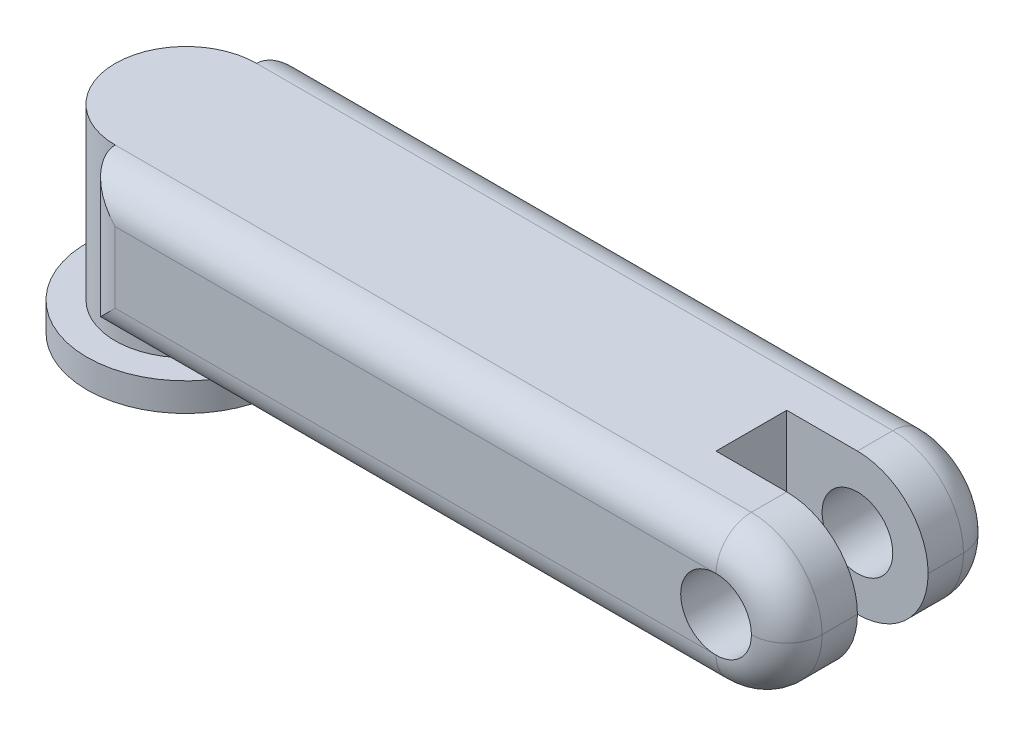
SolidWorks part; units mm, degrees
ref_plane "Front Plane" through (0, 0, 0) normal (0, 0, 1) x (1, 0, 0)
ref_plane "Top Plane" through (0, 0, 0) normal (0, 1, 0) x (1, 0, 0)
ref_plane "Right Plane" through (0, 0, 0) normal (1, 0, 0) x (0, 0, -1)
sketch "Sketch1" plane through (0, 0, 0) normal (0, 1, 0) x (1, 0, 0)
  line L0 (40, 0) -> (40, -2.5)
  line L1 (0, 0) -> (40, 0)
  line L2 (0, 0) -> (0, -7.5)
  line L3 (0, -7.5) -> (50, -7.5)
  line L7 (40, -2.5) -> (50, -2.5)
  line L8 (50, -7.5) -> (50, -2.5)
  dimension "D1" = 50
  dimension "D2" = 7.5
  dimension "D3" = 5
  dimension "D4" = 10
extrude "Boss-Extrude1" add sketch "Sketch1" along normal blind 10
sketch "Sketch2" plane through (0, 0, 2.5) normal (0, 0, -1) x (-1, 0, 0)
  line L0 (-50, 10) -> (-50, 0) construction
  line L1 (-50, 10) -> (-40, 10) construction
  circle A0 centre (-45, 5) radius 2.5
  point P2 (-50, 5)
  dimension "D1" = 5
  dimension "D2" = 5
  dimension "D3" = 5
extrude "Cut-Extrude1" cut sketch "Sketch2" against normal through all
mirror "Mirror1" about plane through (0, 10, 0) normal (0, 0, 1) of "Cut-Extrude1", "Boss-Extrude1"
sketch "Sketch3" plane through (0, 10, 0) normal (0, 1, 0) x (1, 0, 0)
  circle A0 centre (0, 0) radius 5
  dimension "D1" = 10
extrude "Boss-Extrude2" add sketch "Sketch3" against normal blind 12
sketch "Sketch4" plane through (0, -2, 0) normal (0, -1, 0) x (1, 0, 0)
  circle A0 centre (0, 0) radius 7
  dimension "D1" = 14
extrude "Boss-Extrude3" add sketch "Sketch4" along normal blind 2
fillet "Fillet1" radius 5 4 edges at (50, 0, -5) (50, 10, -5) (50, 0, 5) (50, 10, 5)
fillet "Fillet2" radius 2.5 10 edges at (22.5, 10, -7.5) (48.5355, 8.5355, -7.5) (48.5355, 1.4645, -7.5) (22.5, 10, 7.5) (48.5355, 8.5355, 7.5) (48.5355, 1.4645, 7.5) (0, 5, -7.5) (0, 5, 7.5) (22.5, 0, -7.5) (22.5, 0, 7.5)
